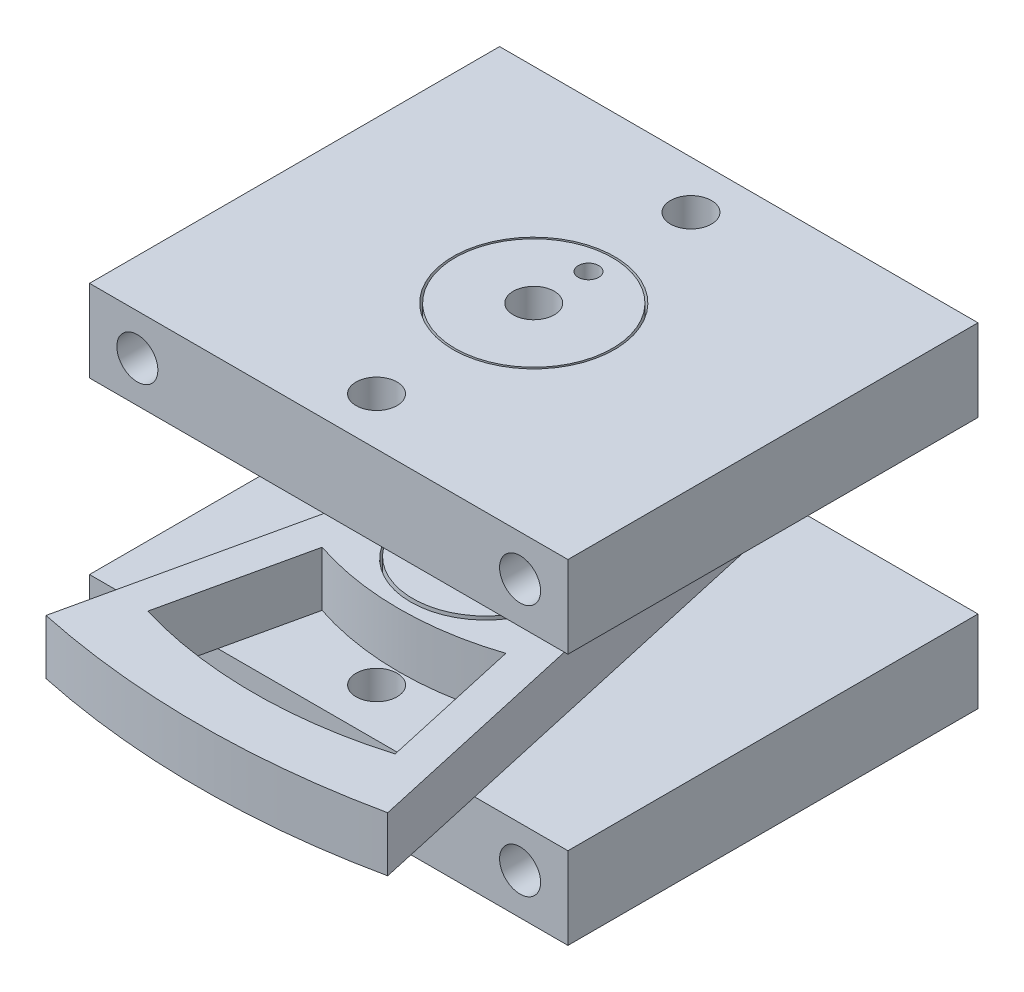
SolidWorks part; units mm, degrees
ref_plane "Front Plane" through (0, 0, 0) normal (0, 0, 1) x (1, 0, 0)
ref_plane "Top Plane" through (0, 0, 0) normal (0, 1, 0) x (1, 0, 0)
ref_plane "Right Plane" through (0, 0, 0) normal (1, 0, 0) x (0, 0, -1)
sketch "Sketch1" plane through (0, 0, 0) normal (0, 1, 0) x (1, 0, 0)
  line L0 (-54.9189, 15) -> (53.8104, 15) construction
  line L1 (-54.9189, 20) -> (53.8104, 20) construction
  line L2 (-59.8011, 0) -> (59.8011, 0) construction
  line L3 (-54.9189, -20) -> (53.8104, -20) construction
  line L8 (-54.9189, -15) -> (53.8104, -15) construction
  line L9 (1.5649, -3.1307) -> (3.7984, -24.0115)
  line L10 (1.5649, -3.1307) -> (0.7141, 4.824) construction
  line L11 (0.7141, 4.824) -> (-0.0304, 11.7843)
  line L12 (0, 3.5) -> (0, 11.5) construction
  line L13 (0, 11.5) -> (-3.4991, 0.0788) construction
  line L14 (-3.4991, 0.0788) -> (-9.6507, -20) construction
  line L15 (0, 11.5) -> (3.4991, 0.0788) construction
  line L16 (3.4991, 0.0788) -> (9.6507, -20) construction
  line L17 (0, 0) -> (-9.6507, -20) construction
  line L18 (0, -3.5) -> (0, -24.5) construction
  line L19 (0, 11.5) -> (0, 4.5)
  line L20 (0, 3.5) -> (0, -3.5) construction
  circle A6 centre (0, 0) radius 3.5 construction
  circle A7 centre (0, 11.5) radius 1.5
  circle A8 centre (0, 0) radius 1.5
  point P2 (0, 11.5)
  point P22 (-2.9587, 0.4959)
  point P25 (-2.5942, 1.4614)
  point P31 (-2.9164, 1)
  point P32 (-4.768, -22.2091)
  point P33 (-2.6919, 1.3242)
  point P34 (-5.5785, -23.4056)
  point P35 (1.7496, -3.5)
  dimension "D5" = 21
  dimension "D3" = 3
  dimension "D4" = 2
  dimension "D7" = 7
  dimension "D8" = 3
  dimension "D1" = 5
  dimension "D2" = 30
  dimension "D6" = 4.5
  dimension "D9" = 19.3013
sketch "Sketch3" plane through (0, 0, 0) normal (0, 1, 0) x (1, 0, 0)
  line L0 (-8.7707, -24.0319) -> (-2.5829, 35.6481) construction
  line L1 (0, -3.5) -> (0, -24.5) construction
  line L2 (0, 35.5) -> (0, -24.5) construction
  line L3 (-9.6507, -20) -> (7.9252, 37.368) construction
  line L4 (-3.4991, 0.0788) -> (-9.6507, -20) construction
  line L5 (-21.2167, -15.0796) -> (2.6867, -22.4029) construction
  line L6 (3.7984, -24.0115) -> (-2.5829, 35.6481) construction
  line L7 (-8.7707, -24.0319) -> (16.0875, -21.373) construction
  arc A0 (-12.5, -23.1835) -> (12.5, -23.1835) centre (0, 35.5) ccw
  arc A1 (-21.2167, -15.0796) -> (2.6867, -22.4029) centre (7.9252, 37.368) ccw
  arc A2 (-8.7707, -24.0319) -> (16.0875, -21.373) centre (-2.5829, 35.6481) ccw
  point P14 (-9.265, -18.7412)
  point P21 (3.6584, -22.7025)
  dimension "D1" = 60
  dimension "D2" = 25
sketch "Sketch2" plane through (0, 0, 0) normal (0, 1, 0) x (1, 0, 0)
  line L0 (0, -9.85) -> (0, -20.5) construction
  line L1 (0, 4.5) -> (0, 11.5) construction
  line L2 (-1.65, 4.5) -> (-1.65, 11.5)
  line L3 (1.65, 4.5) -> (1.65, 11.5)
  line L4 (-4.5385, 12.5123) -> (-12.5, -23.1835)
  line L5 (4.5385, 12.5123) -> (12.5, -23.1835)
  line L6 (6.7225, -8.764) -> (9.0488, -19.194)
  line L8 (-59.8011, 0) -> (59.8011, 0) construction
  line L9 (0, -11.5) -> (0, -18.5) construction
  line L10 (0, -3.5) -> (0, -24.5) construction
  line L11 (-6.7225, -8.764) -> (-9.0488, -19.194)
  circle A0 centre (0, -3.5) radius 5.5
  circle A2 centre (0, 0) radius 1.5 construction
  arc A3 (-1.65, 4.5) -> (1.65, 4.5) centre (0, 4.5) ccw
  arc A4 (1.65, 11.5) -> (-1.65, 11.5) centre (0, 11.5) ccw
  arc A5 (9.0488, -19.194) -> (-9.0488, -19.194) centre (0, 11.5) cw
  circle A6 centre (0, 11.5) radius 1.5 construction
  circle A7 centre (0, 0) radius 1.5
  arc A8 (-4.5385, 12.5123) -> (4.5385, 12.5123) centre (0, 11.5) cw
  arc A9 (12.5, -23.1835) -> (-12.5, -23.1835) centre (0, 35.5) cw
  circle A10 centre (0, 11.5) radius 1.5 construction
  circle A11 centre (0, -11.5) radius 1.5 construction
  arc A12 (6.7225, -8.764) -> (-6.7225, -8.764) centre (0, 11.5) cw
  circle A13 centre (0, -18.5) radius 1.5 construction
  point P9 (0, 8)
  point P17 (0, 0)
  dimension "D1" = 0.5
  dimension "D2" = 0.15
  dimension "D3" = 60
  dimension "D4" = 3
  dimension "D5" = 0.15
  dimension "D8" = 0.5
  dimension "D6" = 2.5
sketch "Sketch6" plane through (0, 0, 0) normal (0, 1, 0) x (1, 0, 0)
  line L0 (0, 0) -> (0, -3.5) construction
  line L1 (0, 0) -> (-3.0311, 1.75) construction
  line L2 (0, 0) -> (3.0311, 1.75) construction
  line L3 (0, 6.1585) -> (0, 1.85) construction
  line L4 (0, 11.5) -> (0, 4.5) construction
  circle A0 centre (0, -3.5) radius 5.35
  circle A1 centre (-3.0311, 1.75) radius 5.35
  circle A2 centre (3.0311, 1.75) radius 5.35
  circle A3 centre (0, -3.5) radius 5.5 construction
  circle A4 centre (0, 4.0043) radius 0.75
  circle A5 centre (3.4678, -2.0021) radius 0.75
  circle A6 centre (-3.4678, -2.0021) radius 0.75
  circle A7 centre (0, 0) radius 1.5 construction
  circle A8 centre (0, 0) radius 1.5
  point P12 (0, 0)
  point P19 (-3.0393, -1.8166)
  point P20 (0, 0)
  point P24 (0, 0)
  dimension "D2" = 0.15
  dimension "D3" = 1.5
  dimension "D1" = 3
extrude "Boss-Extrude2" add sketch "Sketch6" along normal blind 4.15 contours A0 | A8 | A6
extrude "Boss-Extrude3" add sketch "Sketch6<3>" along normal blind 4.15 from surface separate body contours A1 | A8 | A4 | A6 starting at face at (0, 4.15, 1.5)
sketch "Sketch6<3>" plane through (0, 0, 0) normal (0, 1, 0) x (1, 0, 0) same geometry as "Sketch6"
extrude "Boss-Extrude4" add sketch "Sketch6<4>" along normal blind 4.15 from surface separate body contours A2 | A8 | A4 starting at face at (0, 8.3, -3.2543)
sketch "Sketch6<4>" plane through (0, 0, 0) normal (0, 1, 0) x (1, 0, 0) same geometry as "Sketch6"
extrude "Boss-Extrude1" add sketch "Sketch2" along normal blind 4 separate body contours L11 A5 L6 A12 | A0 | L2 A4 L3 A3 | L4 A9 L5 A8
sketch "Sketch7" plane through (0, 0, 0) normal (0, 1, 0) x (1, 0, 0)
  line L1 (-6.8475, 0) -> (6.8475, 0) construction
  line L2 (-54.9189, -15) -> (53.8104, -15) construction
  line L3 (17.5, 15) -> (-17.5, 15)
  line L4 (17.5, 15) -> (17.5, -15)
  line L5 (17.5, -15) -> (-17.5, -15)
  line L6 (-17.5, 15) -> (-17.5, -15)
  line L7 (-54.9189, 15) -> (53.8104, 15) construction
  circle A0 centre (0, 11.5) radius 1.5
  circle A2 centre (0, -11.5) radius 1.5
  circle A3 centre (0, 11.5) radius 1.5 construction
  circle A4 centre (0, 0) radius 5.7543
  circle A5 centre (0, 0) radius 1.5
  circle A6 centre (0, 4.0043) radius 0.75
  circle A7 centre (0, 4.0043) radius 0.75 construction
  circle A8 centre (0, 0) radius 5.9043
  point P19 (0, 15)
  dimension "D2" = 1
  dimension "D1" = 35
  dimension "D3" = 0.15
extrude "Boss-Extrude5" add sketch "Sketch7" against normal blind 6 separate body contours L3 L6 L5 L4 A8 A0 A2 region at (17.039, 0, 0)
extrude "Boss-Extrude6" add sketch "Sketch7<2>" along normal blind 6 from surface separate body contours L3 L6 L5 L4 A8 A0 A2 region at (17.039, 0, 0) starting at face at (0, 12.45, 1.5)
sketch "Sketch7<2>" plane through (0, 0, 0) normal (0, 1, 0) x (1, 0, 0) same geometry as "Sketch7"
extrude "Boss-Extrude7" add sketch "Sketch7<4>" against normal blind 6 separate body contours A4 A6 A5 region at (-5.5915, 0, 0)
sketch "Sketch7<4>" plane through (0, 0, 0) normal (0, 1, 0) x (1, 0, 0) same geometry as "Sketch7"
extrude "Boss-Extrude8" add sketch "Sketch7<5>" along normal blind 6 from surface separate body contours A4 A6 A5 region at (-5.5915, 0, 0) starting at face at (0, 12.45, 1.5)
sketch "Sketch7<5>" plane through (0, 0, 0) normal (0, 1, 0) x (1, 0, 0) same geometry as "Sketch7"
sketch "Sketch9" plane through (0, 0, -15) normal (0, 0, -1) x (-1, 0, 0)
  line L0 (-17.5, 18.45) -> (17.5, 12.45) construction
  line L1 (-14, 15.45) -> (14, 15.45) construction
  line L3 (-17.5, 18.45) -> (-17.5, 12.45) construction
  line L4 (-17.5, 12.45) -> (17.5, 0) construction
  line L5 (0, 6.225) -> (16.5179, 6.225) construction
  circle A0 centre (-14, 15.45) radius 1.5
  circle A1 centre (14, 15.45) radius 1.5
  circle A2 centre (14, -3) radius 1.5
  circle A3 centre (-14, -3) radius 1.5
  point P6 (0, 15.45)
  dimension "D1" = 3
  dimension "D2" = 2
extrude "Cut-Extrude2" cut sketch "Sketch9" against normal through all both
sketch "Sketch10" plane through (0, -6, 0) normal (0, -1, 0) x (1, 0, 0)
  circle A0 centre (9.7556, 0) radius 1.8125
  circle A1 centre (-9.5953, 0) radius 1.8125
  point P4 (9.7556, 0)
  point P5 (-9.5953, 0)
